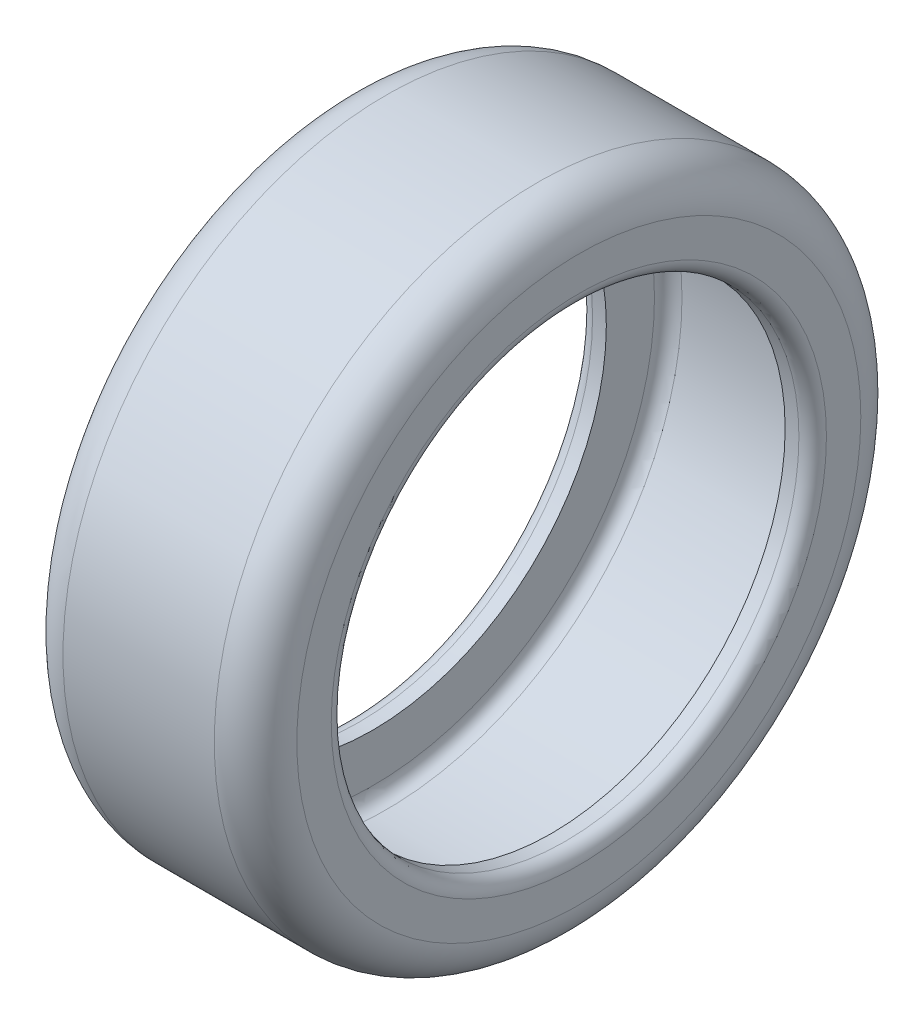
SolidWorks part; units mm, degrees
ref_plane "Front Plane" through (0, 0, 0) normal (0, 0, 1) x (1, 0, 0)
ref_plane "Top Plane" through (0, 0, 0) normal (0, 1, 0) x (1, 0, 0)
ref_plane "Right Plane" through (0, 0, 0) normal (1, 0, 0) x (0, 0, -1)
sketch "Sketch1" plane through (0, 0, 0) normal (1, 0, 0) x (0, 0, -1)
  circle A0 centre (0, 0) radius 17
  circle A1 centre (0, 0) radius 23.5
  dimension "D1" = 34
  dimension "D2" = 47
extrude "Boss-Extrude2" add sketch "Sketch1" along normal blind 17
fillet "Fillet1" radius 3 2 edges at (0, 0, -23.5) (17, 0, -23.5)
fillet "Fillet2" radius 1 2 edges at (0, 0, -17) (17, 0, -17)
shell "Shell1" thickness 2 removed face at (1, 0, -17)
